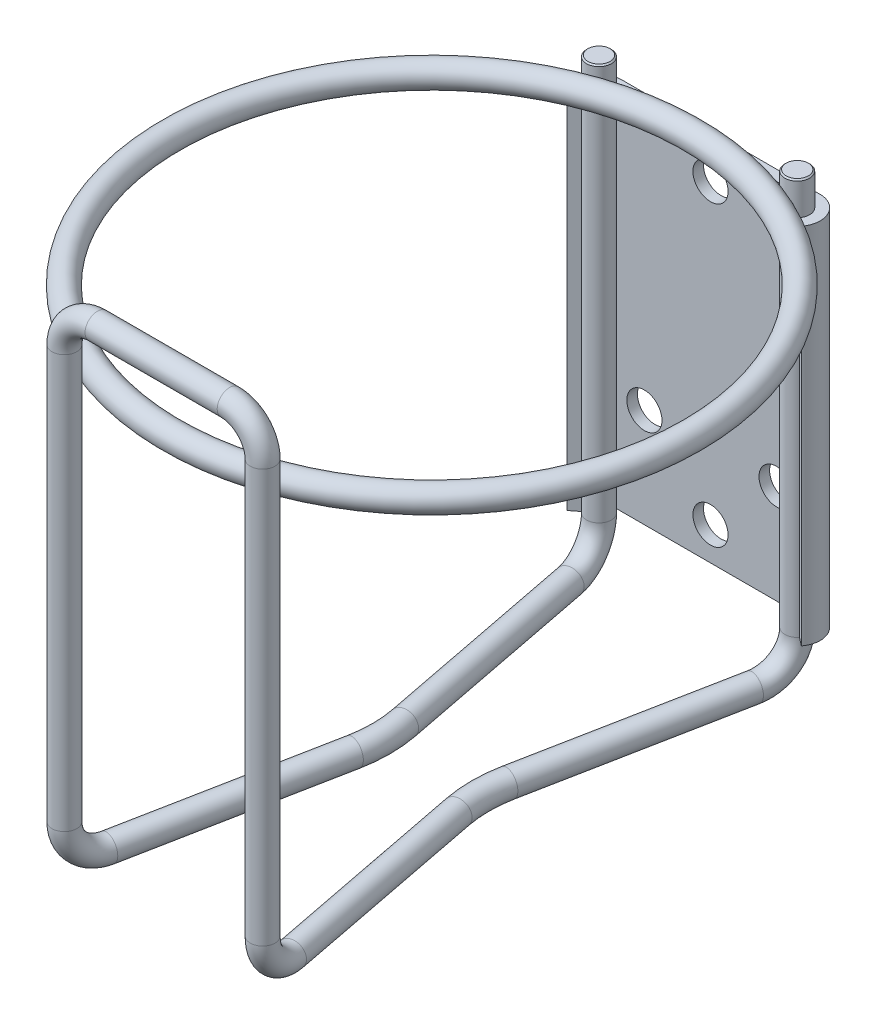
SolidWorks part; units mm, degrees
ref_plane "Front" through (0, 0, 0) normal (0, 0, 1) x (1, 0, 0)
ref_plane "Top" through (0, 0, 0) normal (0, 1, 0) x (1, 0, 0)
ref_plane "Right" through (0, 0, 0) normal (1, 0, 0) x (0, 0, -1)
sketch "Sketch1" plane through (0, 0, 0) normal (0, 0, 1) x (1, 0, 0)
  line L0 (-12.7, -15.875) -> (12.7, -15.875) construction
  line L1 (19.05, -34.925) -> (-19.05, -34.925)
  line L2 (19.05, -34.925) -> (19.05, 34.925)
  line L3 (19.05, 34.925) -> (-19.05, 34.925)
  line L4 (-19.05, -34.925) -> (-19.05, 34.925)
  line L5 (19.05, -34.925) -> (-19.05, 34.925) construction
  line L6 (19.05, 34.925) -> (-19.05, -34.925) construction
  line L7 (-12.7, -15.875) -> (0, -28.575) construction
  line L8 (0, 28.575) -> (0, -28.575) construction
  line L9 (0, 31.9532) -> (0, 34.925) construction
  line L10 (0, -31.9532) -> (0, -34.925) construction
  line L12 (0, -42.8625) -> (0, -47.625) construction
  circle A0 centre (0, 28.575) radius 3.3782
  circle A1 centre (0, -28.575) radius 3.3782
  circle A2 centre (-12.7, -15.875) radius 3.3782
  circle A3 centre (12.7, -15.875) radius 3.3782
  point P0 (0, 0)
  point P14 (0, -15.875)
  dimension "D5" = 6.7564
  dimension "D1" = 57.15
  dimension "D2" = 25.4
  dimension "D3" = 45
  dimension "D4" = 4.7625
  dimension "D6" = 69.85
  dimension "D7" = 38.1
  dimension "Overall Height" = 82.55
extrude "Boss-Extrude1" add sketch "Sketch1" against normal blind 2.032
sketch "Sketch15" plane through (0, 0, 0) normal (0, 1, 0) x (1, 0, 0)
  line L4 (19.05, 0) -> (19.05, -4.7625) construction
  circle A0 centre (0, -53.5636) radius 52.3875 construction
  dimension "D1" = 104.775
  dimension "D2" = 4.7625
sketch "Sketch4" plane through (19.05, 0, 0) normal (1, 0, 0) x (0, 0, -1)
  line L0 (-2.3813, 41.275) -> (-2.3812, -34.925)
  line L1 (-105.1242, -34.925) -> (-2.3812, -34.925) construction
  line L2 (-105.1242, -34.925) -> (-105.1242, 41.275) construction
  line L3 (-107.5055, 41.275) -> (-102.743, 41.275) construction
  line L4 (-4.7625, 41.275) -> (0, 41.275) construction
  line L5 (-53.7527, -39.6875) -> (-53.7527, -44.45) construction
  line L7 (0, -34.925) -> (0, 34.925) construction
  line L8 (-105.1242, 41.275) -> (-105.1242, 53.975) construction
  line L11 (2.032, -34.925) -> (2.032, 34.925) construction
  line L24 (2.032, 34.925) -> (0, 34.925) construction
  point P1 (-53.7527, -34.925)
  point P2 (-53.7527, -42.0688)
  point P8 (-105.1242, 41.275)
  point P11 (1.016, 34.925)
  point P12 (-2.3813, 41.275)
  dimension "D1" = 6.35
  dimension "D2" = 19.05
  dimension "D3" = 98.425
  dimension "D4" = 4.7625
  dimension "D5" = 109.5375
ref_plane "Plane1" through (0, 41.275, 0) normal (0, 1, 0) x (1, 0, 0)
sketch "Sketch5" plane through (0, 41.275, 0) normal (0, -1, 0) x (1, 0, 0)
  line L0 (-19.05, 0) -> (19.05, 0) construction
  circle A0 centre (19.05, 2.3813) radius 2.3813
  dimension "D1" = 4.7625
sweep "Sweep7" add profiles "Sketch5" path "Sketch4"
ref_plane "Plane2" through (0, -42.0688, 0) normal (0, 1, 0) x (1, 0, 0)
sketch "Sketch8" plane through (0, -42.0688, 0) normal (0, 1, 0) x (1, 0, 0)
  line L0 (19.05, -2.3813) -> (9.9932, -48.8986)
  line L2 (19.05, -4.7625) -> (19.05, 0) construction
  line L6 (0, 0) -> (0, -107.5055) construction
  line L7 (9.525, -53.7527) -> (0, -53.7527) construction
  arc A0 (9.9932, -48.8986) -> (9.525, -53.7527) centre (34.925, -53.7527) ccw
  point P4 (0, -53.7527)
  point P13 (9.525, -53.7527)
  dimension "D2" = 25.4
  dimension "D1" = 19.05
ref_plane "Plane3" through (18.8009, 0, 3.6605) normal (-0.9816, 0, -0.1911) x (-0.1911, 0, 0.9816)
sketch "Sketch9" plane through (18.8009, 0, 3.6605) normal (-0.9816, 0, -0.1911) x (-0.1911, 0, 0.9816)
  line L1 (-3.6845, -34.925) -> (1.078, -34.925) construction
  line L2 (49.1214, -42.0688) -> (5.8405, -42.0688) construction
  line L3 (-1.3033, -34.925) -> (-1.3033, 0) construction
  arc A0 (5.8405, -42.0688) -> (-1.3033, -34.925) centre (5.8405, -34.925) cw
sketch "Sketch10" plane through (0, -34.925, 0) normal (0, -1, 0) x (1, 0, 0)
  circle A0 centre (19.05, 2.3812) radius 2.3813 construction
  circle A2 centre (19.05, 2.3812) radius 2.3813
sweep "Sweep4" add profiles "Sketch10" path "Sketch9"
ref_plane "Plane4" through (0, 0, 53.7527) normal (0, 0, 1) x (1, 0, 0)
sketch "Sketch11" plane through (-1.1162, 0, 5.7328) normal (-0.1911, 0, 0.9816) x (0.9816, 0, 0.1911)
  circle A1 centre (19.154, -42.0688) radius 2.3813
  circle A2 centre (19.154, -42.0688) radius 2.3813
  dimension "D1" = 0
sweep "Sweep5" add profiles "Sketch11" path "Sketch8"
mirror "Mirror8" about plane through (9.525, -42.0688, 53.7527) normal (0, 0, 1) of bodies 121
mirror "Mirror6" about plane through (0, 0, 0) normal (1, 0, 0) of bodies 129 124
ref_plane "Plane5" through (0, 0, 105.1242) normal (0, 0, 1) x (1, 0, 0)
sketch "Sketch16" plane through (0, 41.275, 0) normal (0, 1, 0) x (1, 0, 0)
  circle A0 centre (-19.05, -105.1242) radius 2.3813 construction
  circle A1 centre (19.05, -105.1242) radius 2.3813 construction
  circle A2 centre (-19.05, -105.1242) radius 2.3813
  circle A3 centre (19.05, -105.1242) radius 2.3813
extrude "Cut-Extrude2" cut sketch "Sketch16" against normal blind 3.175 contours A2 | A3
sketch "Sketch13" plane through (0, 0, 105.1242) normal (0, 0, 1) x (1, 0, 0)
  line L0 (-12.7, 50.8) -> (12.7, 50.8)
  line L1 (19.05, 41.275) -> (19.05, 53.975) construction
  line L2 (-19.05, 44.45) -> (-19.05, -34.925) construction
  line L3 (-21.4313, -34.925) -> (-16.6688, -34.925) construction
  line L5 (-19.05, 44.45) -> (-19.05, 38.1)
  line L6 (0, 53.975) -> (0, 47.625) construction
  line L7 (19.05, 44.45) -> (19.05, 38.1)
  line L8 (19.05, 44.45) -> (19.05, -34.925) construction
  line L9 (19.05, -34.925) -> (19.05, 41.275) construction
  line L11 (21.4313, 38.1) -> (16.6688, 38.1) construction
  arc A0 (-12.7, 50.8) -> (-19.05, 44.45) centre (-12.7, 44.45) ccw
  arc A1 (12.7, 50.8) -> (19.05, 44.45) centre (12.7, 44.45) cw
  point P12 (0, 50.8)
  point P13 (0, 50.8)
  point P19 (19.05, 50.8)
  dimension "D2" = 6.35
  dimension "D1" = 6.35
sketch "Sketch14" plane through (0, 38.1, 0) normal (0, 1, 0) x (1, 0, 0)
  circle A2 centre (19.05, -105.1243) radius 2.3813
  circle A4 centre (19.05, -105.1243) radius 2.3813 construction
sweep "Sweep9" add profiles "Sketch14" path "Sketch13"
ref_plane "Plane6" through (0, 38.1, 0) normal (0, 1, 0) x (1, 0, 0)
sketch "Sketch6" plane through (0, 38.1, 0) normal (0, 1, 0) x (1, 0, 0)
  circle A0 centre (0, -53.5636) radius 50.0062
  circle A2 centre (0, -53.5636) radius 52.3875 construction
  circle A3 centre (0, -53.5636) radius 47.625 construction
  circle A10 centre (0, -53.5636) radius 52.3875 construction
  dimension "D3" = 104.775
  dimension "D4" = 95.25
  dimension "D2" = 2.3813
  dimension "D1" = 2.3813
sketch "Sketch7" plane through (0, 0, 0) normal (1, 0, 0) x (0, 0, -1)
  circle A0 centre (-3.5574, 38.1) radius 2.3812
  dimension "D1" = 4.7625
sweep "Sweep8" add profiles "Sketch7" path "Sketch6"
sketch "Sketch18" plane through (0, 34.925, 0) normal (0, 1, 0) x (1, 0, 0)
  line L0 (19.05, 0) -> (-19.05, 0) construction
  line L1 (-20.9341, -3.8374) -> (-22.5419, -5.08)
  line L2 (19.05, 2.032) -> (-19.05, 2.032) construction
  line L3 (-19.05, 2.032) -> (-19.05, 0) construction
  line L4 (-19.05, 2.032) -> (-19.05, 0)
  arc A0 (-19.05, 0) -> (-20.9341, -3.8374) centre (-19.05, -2.3813) ccw
  circle A1 centre (-19.05, -2.3813) radius 2.3813 construction
  arc A2 (-22.5419, -5.08) -> (-19.05, 2.032) centre (-19.05, -2.3813) cw
  circle A3 centre (-19.05, -2.3812) radius 2.3813 construction
  dimension "D1" = 5.08
extrude "Boss-Extrude8" add sketch "Sketch18" against normal up to surface (69.85 mm away) separate body up to face at (0, -34.925, -1.016)
mirror "Mirror9" about plane through (0, 0, 0) normal (1, 0, 0) of bodies 137
combine bodies "Combine1" operation type add bodies to combine 137 109 138
chamfer "Chamfer1" distance 0.254 angle 45 2 edges at (-19.05, 41.275, 0) (19.05, 41.275, 0)
